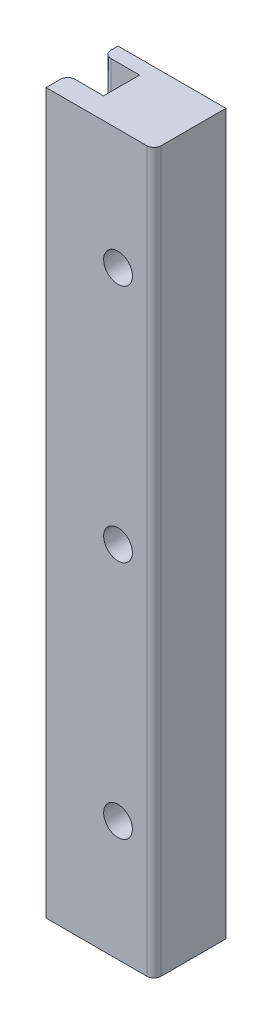
SolidWorks part; units mm, degrees
ref_plane "Front Plane" through (0, 0, 0) normal (0, 0, 1) x (1, 0, 0)
ref_plane "Top Plane" through (0, 0, 0) normal (0, 1, 0) x (1, 0, 0)
ref_plane "Right Plane" through (0, 0, 0) normal (1, 0, 0) x (0, 0, -1)
sketch "Sketch1" plane through (0, 0, 0) normal (0, 1, 0) x (1, 0, 0)
  line L0 (-24.9296, 0) -> (27.7465, 0) construction
  line L1 (0, -18.0986) -> (0, -7) construction
  line L2 (0, 0) -> (15, 0)
  line L3 (15, 0) -> (15, -2)
  line L6 (7, -10) -> (0, -10)
  line L7 (0, -10) -> (0, -7)
  line L8 (0, -7) -> (5, -7)
  line L9 (5, -7) -> (5, -2)
  line L10 (5, -2) -> (0, -2)
  line L11 (0, -2) -> (0, 18.662) construction
  line L12 (0, -2) -> (0, 0)
  line L13 (7, -10) -> (15, -10)
  line L14 (15, -10) -> (15, -2)
  dimension "D1" = 15
  dimension "D2" = 2
  dimension "D3" = 3
  dimension "D4" = 5
  dimension "D6" = 2
  dimension "D7" = 5
extrude "Boss-Extrude1" add sketch "Sketch1" along normal blind 100
fillet "Fillet1" radius 1 3 edges at (0, 50, 7) (0, 50, 2) (15, 50, 10)
sketch "Sketch2" plane through (0, 0, 10) normal (0, 0, 1) x (1, 0, 0)
  line L0 (10, 100) -> (10, 0) construction
  line L1 (0, 100) -> (14, 100) construction
  line L2 (0, 0) -> (14, 0) construction
  line L3 (0, 100) -> (0, 0) construction
  line L4 (0, 50) -> (12, 50) construction
  circle A0 centre (10, 50) radius 2
  circle A1 centre (10, 83.3) radius 2
  circle A2 centre (10, 50) radius 2
  circle A3 centre (10, 16.7) radius 2
  dimension "D2" = 4
  dimension "D1" = 10
  dimension "D3" = 2
  dimension "D4" = 2
extrude "Cut-Extrude1" cut sketch "Sketch2" against normal blind 10 contours A3 | A1 | A0 region at (10, 16.7, 10)
